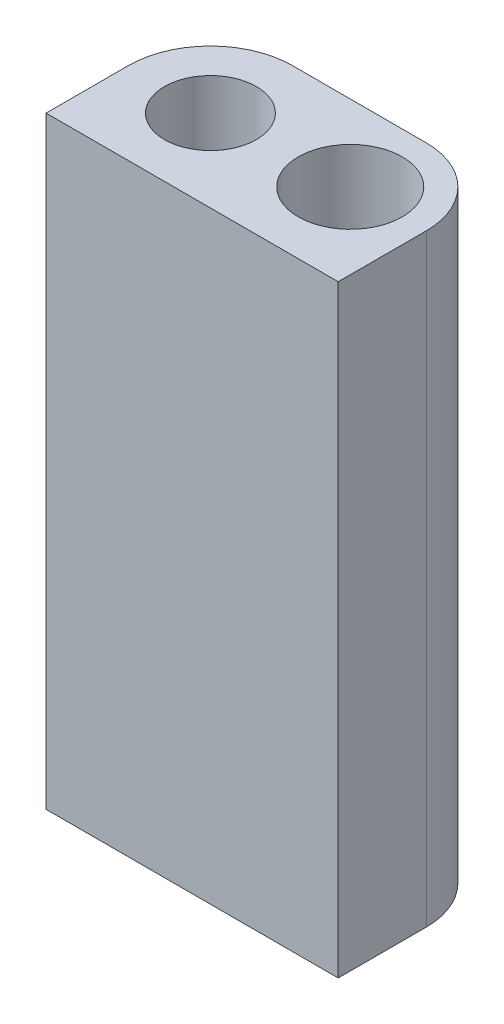
SolidWorks part; units mm, degrees
ref_plane "Front Plane" through (0, 0, 0) normal (0, 0, 1) x (1, 0, 0)
ref_plane "Top Plane" through (0, 0, 0) normal (0, 1, 0) x (1, 0, 0)
ref_plane "Right Plane" through (0, 0, 0) normal (1, 0, 0) x (0, 0, -1)
sketch "Sketch1" plane through (0, 0, 0) normal (0, 1, 0) x (1, 0, 0)
  line L0 (0, -5.995) -> (0, 5.995) construction
  line L1 (-5.45, 0) -> (3.05, 0)
  line L2 (-5.45, 0) -> (-5.45, -5.45)
  line L3 (-5.45, -5.45) -> (5.45, -5.45)
  line L5 (3.05, 0) -> (5.45, 0) construction
  line L6 (0, 5.45) -> (8.8767, 5.45)
  line L7 (13.9267, 0.4) -> (13.9267, -5.45)
  line L8 (13.9267, -5.45) -> (5.45, -5.45)
  line L10 (0, -3.05) -> (8.8767, -3.05) construction
  line L11 (0, -3.05) -> (0, -5.45)
  circle A0 centre (0, 0) radius 3.05
  circle A2 centre (8.8767, 0.4) radius 3.45
  arc A3 (13.9267, 0.4) -> (8.8767, 5.45) centre (8.8767, 0.4) ccw
  arc A4 (0, 5.45) -> (-5.45, 0) centre (0, 0) ccw
  point P8 (0, -5.45)
  dimension "D1" = 6.1
  dimension "D2" = 2.4
  dimension "D3" = 6.9
  dimension "D4" = 10.1
  dimension "D5" = 2.4
extrude "Boss-Extrude2" add sketch "Sketch1" along normal blind 40 contours L6 A4 L1 A0 L11 L3 L8 L7 A3 A2 | A0 L1 L2 L3 L11 region at (5.3619, 0, -0.0534) region at (-3.1917, 0, 3.1917)
